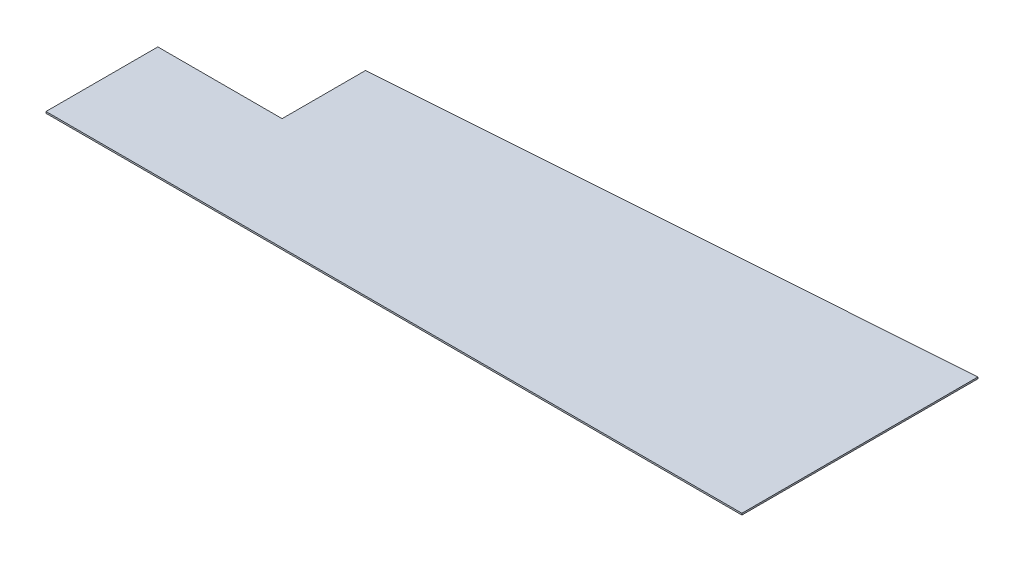
SolidWorks part; units mm, degrees
material "6061 Alloy"
ref_plane "Front Plane" through (0, 0, 0) normal (0, 0, 1) x (1, 0, 0)
ref_plane "Top Plane" through (0, 0, 0) normal (0, 1, 0) x (1, 0, 0)
ref_plane "Right Plane" through (0, 0, 0) normal (1, 0, 0) x (0, 0, -1)
sketch "Sketch1" plane through (0, 0, 0) normal (0, 1, 0) x (1, 0, 0)
  line L0 (0, 0) -> (280, 0)
  line L1 (0, 45) -> (0, 0)
  line L3 (280, 95) -> (280, 0)
  line L4 (50, 78.5721) -> (50, 45)
  line L5 (50, 45) -> (0, 45)
  line L7 (50, 78.5721) -> (280, 95)
  dimension "D1" = 45
  dimension "D2" = 280
  dimension "D3" = 95
  dimension "D4" = 50
  dimension "D5" = 33.5721
sheet metal parameters "Sheet-Metal1" thickness 0.65 parameters "D1"=0.7366
base flange "Vertical Wall" sketch "Sketch1" thickness 0.65 reverse thickness direction no parameters "D1"=0.7366
flat pattern "Flat-Pattern1" [suppressed]
sketch "Bend-Lines1" plane through (0, 0, 0) normal (0, 1, 0) x (1, 0, 0)
  point P0 (93.1821, -1.7566)
  point P1 (103.1821, -1.7566)
  point P2 (239.2046, -1.7566)
  point P3 (249.2046, -1.7566)
  point P4 (357.0941, -1.02)
  point P5 (377.0941, -1.02)
  point P6 (-76.9773, -1.02)
  point P7 (-56.9773, -1.02)
  point P8 (281.047, 0)
  point P9 (281.047, 94.9716)
  point P10 (-0.9887, 60.0001)
  point P11 (-0.9887, 0)
sketch3d "Bounding-Box1" [suppressed]
  line L0 (383.1845, -15.1242, 0) -> (-75.2412, -40.9331, 0) construction
  line L1 (376.6789, 100.4309, 0) -> (-81.7468, 74.622, 0) construction
  line L2 (383.1845, -15.1242, 0) -> (376.6789, 100.4309, 0) construction
  line L3 (-75.2412, -40.9331, 0) -> (-81.7468, 74.622, 0) construction
